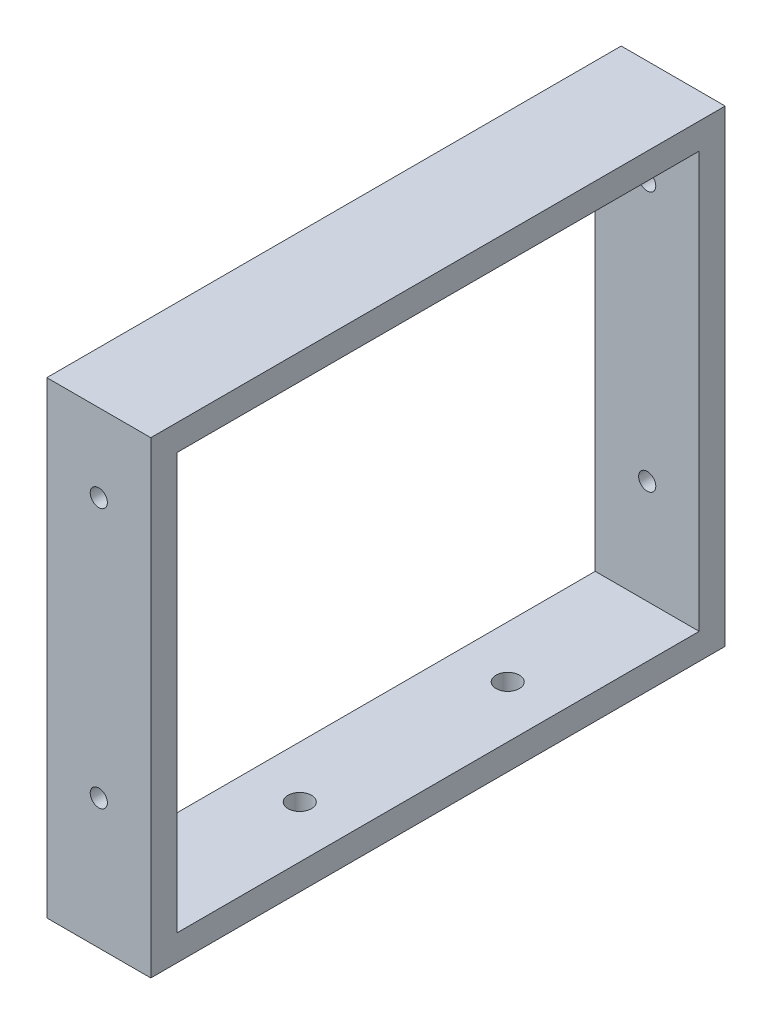
SolidWorks part; units mm, degrees
ref_plane "Front Plane" through (0, 0, 0) normal (0, 0, 1) x (1, 0, 0)
ref_plane "Top Plane" through (0, 0, 0) normal (0, 1, 0) x (1, 0, 0)
ref_plane "Right Plane" through (0, 0, 0) normal (1, 0, 0) x (0, 0, -1)
sketch "Sketch1" plane through (0, 0, 0) normal (1, 0, 0) x (0, 0, -1)
  line L1 (-55.2375, -45) -> (55.2375, -45)
  line L2 (-55.2375, -45) -> (-55.2375, 45)
  line L3 (-55.2375, 45) -> (55.2375, 45)
  line L4 (55.2375, -45) -> (55.2375, 45)
  line L5 (-55.2375, -45) -> (55.2375, 45) construction
  line L6 (-55.2375, 45) -> (55.2375, -45) construction
  line L7 (-50.2375, -40) -> (50.2375, -40)
  line L8 (-50.2375, -40) -> (-50.2375, 40)
  line L9 (-50.2375, 40) -> (50.2375, 40)
  line L10 (50.2375, -40) -> (50.2375, 40)
  line L11 (-50.2375, -40) -> (50.2375, 40) construction
  line L12 (-50.2375, 40) -> (50.2375, -40) construction
  line L13 (20.2375, -40) -> (25.2375, -40)
  line L14 (20.2375, -40) -> (20.2375, 40)
  line L15 (20.2375, 40) -> (25.2375, 40)
  line L16 (25.2375, -40) -> (25.2375, 40)
  line L17 (20.2375, -40) -> (25.2375, 40) construction
  line L18 (20.2375, 40) -> (25.2375, -40) construction
  point P0 (0, 0)
  point P6 (0, 0)
  point P11 (22.7375, 0)
  dimension "D1" = 110.475
  dimension "D2" = 90
  dimension "D3" = 5
  dimension "D4" = 5
  dimension "D5" = 5
  dimension "D6" = 25
extrude "Boss-Extrude1" add sketch "Sketch1" along normal blind 20 contours L1 L4 L3 L2 L10 L7 L8 L9 | L7 L16 L9 L14 region at (0, 0, 53.8126) region at (0, 0, -22.7375)
hole_wizard "M4 Clearance Hole1" positions "Sketch2" profile "Sketch3" hole size "M4" standard "ANSI Metric"
sketch "Sketch2" plane through (0, -40, 0) normal (0, 1, 0) x (1, 0, 0)
  line L0 (10, 23.4125) -> (10, -16.5875)
  line L2 (0, -55.2375) -> (0, 55.2375) construction
  point P1 (10, 23.4125)
  point P2 (10, -16.5875)
  dimension "D1" = 40
  dimension "D2" = 10
  dimension "D3" = 31.825
sketch "Sketch3" plane through (10, -40, -23.4125) normal (1, 0, 0) x (0, 0, 1)
  line L0 (0, 0) -> (0, 9.1519)
  line L1 (0, 9.1519) -> (2.25, 7.8)
  line L2 (2.25, 7.8) -> (2.25, 0)
  line L5 (2.25, 0) -> (0, 0)
  line L10 (0, 9.1519) -> (-2.25, 7.8) construction
  line L11 (0, -6.35) -> (0, 107.95) construction
  dimension "Hole Dia." = 4.5
  dimension "Hole Depth" = 7.8
  dimension "Drill Angle" = 118
hole_wizard "M4x0.7 Tapped Hole1" positions "Sketch4" profile "Sketch6" tap size "M4x0.7" standard "ANSI Metric"
sketch "Sketch4" plane through (0, 0, 55.2375) normal (0, 0, 1) x (1, 0, 0)
  line L0 (10, 30) -> (10, -20)
  line L2 (0, -45) -> (0, 45) construction
  line L3 (20, -45) -> (0, -45) construction
  point P0 (10, 30)
  point P1 (10, -20)
  dimension "D1" = 50
  dimension "D2" = 10
  dimension "D3" = 25
sketch "Sketch6" plane through (10, 30, 55.2375) normal (1, 0, 0) x (0, -1, 0)
  line L0 (0, 0) -> (0, 11.0914)
  line L1 (0, 11.0914) -> (1.65, 10.1)
  line L2 (1.65, 10.1) -> (1.65, 0)
  line L5 (1.65, 0) -> (0, 0)
  line L10 (0, 11.0914) -> (-1.65, 10.1) construction
  line L11 (0, -6.35) -> (0, 107.95) construction
  dimension "Tap Drill Dia." = 3.3
  dimension "Tap Drill Depth" = 10.1
  dimension "Drill Angle" = 118
cosmetic thread "Hole Thread1" parameters "D1"=8, "D2"=4
cosmetic thread "Hole Thread2" parameters "D1"=8, "D2"=4
mirror "Mirror1" about plane through (0, 0, 0) normal (0, 0, 1) of "M4x0.7 Tapped Hole1"
cosmetic thread "Hole Thread3" parameters "D1"=8, "D2"=4
cosmetic thread "Hole Thread4" parameters "D1"=8, "D2"=4
sketch "Sketch7" plane through (0, 0, 0) normal (-1, 0, 0) x (0, 0, 1)
  line L1 (-25.2375, 40) -> (-20.2375, 40)
  line L2 (-25.2375, 40) -> (-25.2375, -40)
  line L3 (-25.2375, -40) -> (-20.2375, -40)
  line L4 (-20.2375, 40) -> (-20.2375, -40)
extrude "Cut-Extrude1" cut sketch "Sketch7" against normal blind 30
